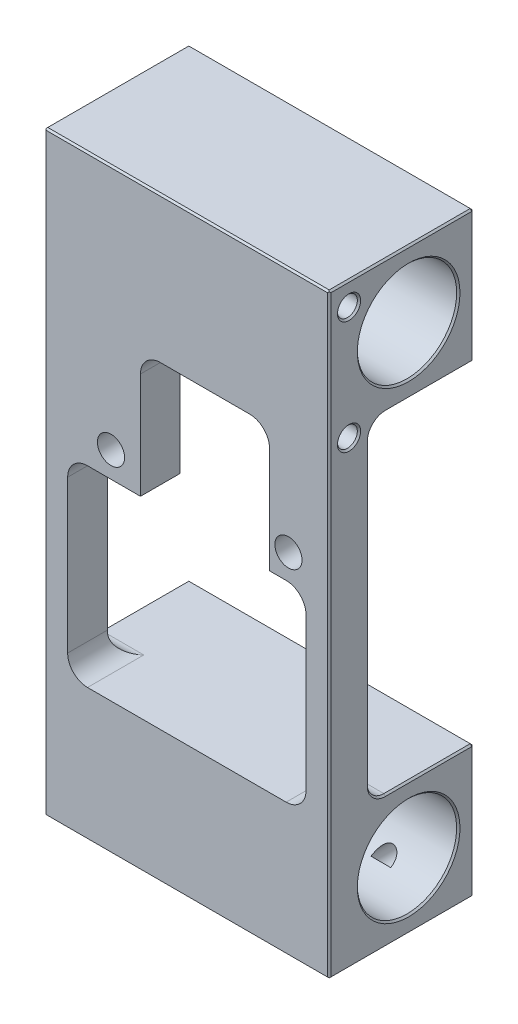
SolidWorks part; units mm, degrees
ref_plane "Спереди" through (0, 0, 0) normal (0, 0, 1) x (1, 0, 0)
ref_plane "Сверху" through (0, 0, 0) normal (0, 1, 0) x (1, 0, 0)
ref_plane "Справа" through (0, 0, 0) normal (1, 0, 0) x (0, 0, -1)
sketch "Model" plane through (0, 0, 0) normal (0, 0, 1) x (1, 0, 0)
  line L0 (0, 90) -> (0, 0)
  line L1 (0, 0) -> (43, 0)
  line L2 (43, 0) -> (43, 90)
  line L3 (43, 90) -> (0, 90)
  line L4 (14.5, 49) -> (14.5, 68)
  line L5 (3.5, 49) -> (14.5, 49)
  line L6 (3.5, 49) -> (3.5, 20)
  line L7 (3.5, 20) -> (39.5, 20)
  line L8 (39.5, 49) -> (39.5, 20)
  line L9 (14.5, 68) -> (34, 68)
  line L10 (34, 68) -> (34, 49)
  line L11 (10.05, 52.85) -> (38.067, 52.85) construction
  line L12 (34, 49) -> (39.5, 49)
  circle A0 centre (10.05, 52.85) radius 2.05
  circle A1 centre (36.85, 52.85) radius 2.05
  dimension "D10" = 4.1
  dimension "D1" = 20
  dimension "D2" = 29
  dimension "D3" = 90
  dimension "D4" = 36
  dimension "D5" = 3.5
  dimension "D6" = 43
  dimension "D7" = 14.5
  dimension "D8" = 9
  dimension "D9" = 22
  dimension "D11" = 4.45
  dimension "D12" = 3.85
  dimension "D13" = 2.85
  dimension "D14" = 26.8
extrude "Бобышка-Вытянуть1" add sketch "Model" along normal blind 21.8
fillet "Скругление1" radius 3 6 edges at (3.5, 20, 10.9) (39.5, 20, 10.9) (39.5, 49, 10.9) (34, 68, 10.9) (14.5, 68, 10.9) (3.5, 49, 10.9)
sketch "Эскиз2" plane through (43, 0, 0) normal (1, 0, 0) x (0, 0, -1)
  line L0 (0, 70) -> (-15.8, 70)
  line L1 (0, 0) -> (0, 90) construction
  line L2 (-15.8, 70) -> (-15.8, 20)
  line L3 (-15.8, 20) -> (0, 20)
  line L4 (-21.8, 90) -> (0, 90) construction
  line L5 (-21.8, 0) -> (0, 0) construction
  line L6 (-21.8, 0) -> (-21.8, 90) construction
  dimension "D1" = 20
  dimension "D2" = 20
  dimension "D3" = 6
extrude "Вырез-Вытянуть1" cut sketch "Эскиз2" against normal through all and the other way through all
fillet "Скругление2" radius 2.5 3 edges at (21.5, 70, 15.8) (39.75, 20, 15.8) (3.25, 20, 15.8)
sketch "Эскиз3" plane through (43, 0, 0) normal (1, 0, 0) x (0, 0, -1)
  line L0 (-21.8, 45) -> (2.0863, 45) construction
  line L1 (-21.8, 0) -> (-21.8, 90) construction
  line L2 (-18.8, 90) -> (-18.8, 38.6194) construction
  line L3 (-21.8, 90) -> (0, 90) construction
  circle A0 centre (-9.8, 80) radius 7.5
  circle A5 centre (-9.8, 10) radius 7.5
  circle A6 centre (-18.8, 86.5) radius 1.5
  circle A7 centre (-18.8, 69.4) radius 1.5
  dimension "D1" = 15
  dimension "D5" = 3
  dimension "D10" = 3
  dimension "D4" = 12
  dimension "D6" = 3
  dimension "D7" = 3.5
  dimension "D9" = 17.1
  dimension "D8" = 2
extrude "Вырез-Вытянуть2" cut sketch "Эскиз3" against normal through all contours A5 | A0 region at (43, 80, 9.8) region at (43, 10, 9.8)
extrude "Вырез-Вытянуть5" cut sketch "Эскиз3<6>" against normal blind 18 contours A6 | A7 region at (43, 86.5, 18.8) region at (43, 69.4, 18.8)
sketch "Эскиз3<6>" plane through (43, 0, 0) normal (1, 0, 0) x (0, 0, -1) same geometry as "Эскиз3"
sketch "Эскиз8" plane through (0, 0, 0) normal (0, 0, -1) x (-1, 0, 0)
  line L0 (-43, 86.5) -> (0, 86.5) construction
  line L1 (-43, 70) -> (-43, 90) construction
  line L2 (-43, 90) -> (0, 90) construction
  line L3 (-21.5, 92.9275) -> (-21.5, 81.0804) construction
  line L4 (0, 90) -> (0, 70) construction
  line L5 (-55.1775, 45) -> (12.5287, 45) construction
  line L6 (0, 0) -> (-43, 0) construction
  line L7 (-43, 0) -> (-43, 20) construction
  circle A0 centre (-35, 86.5) radius 1.5
  circle A1 centre (-8, 86.5) radius 1.5
  circle A2 centre (-8, 3.5) radius 1.5
  circle A3 centre (-35, 3.5) radius 1.5
  dimension "D2" = 3
  dimension "D1" = 3.5
  dimension "D3" = 8
  dimension "D4" = 8
  dimension "D5" = 3.5
  dimension "D6" = 8
extrude "Вырез-Вытянуть7" cut sketch "Эскиз8" against normal blind 6
chamfer "Фаска3" distance 0.25 angle 45 34 edges at (33.5, 86.5, 0) (9.5, 86.5, 0) (36.5, 3.5, 0) (6.5, 3.5, 0) (0, 17.5, 9.8) (0, 87.5, 9.8) (21.5, 90, 0) (21.5, 70, 0) (21.5, 0, 0) (0, 80, 0) (0, 90, 10.9) (0, 45, 21.8) (0, 0, 10.9) (0, 10, 0) (0, 70, 6.65) (0, 69.2678, 15.0678) (0, 45, 15.8) (0, 20.7322, 15.0678) (0, 20, 6.65) (21.5, 20, 0) (43, 69.2678, 15.0678) (43, 45, 15.8) (43, 20.7322, 15.0678) (43, 20, 6.65) (43, 10, 0) (43, 0, 10.9) (43, 45, 21.8) (43, 90, 10.9) (43, 80, 0) (43, 70, 6.65) (43, 17.5, 9.8) (43, 87.5, 9.8) (43, 88, 18.8) (43, 70.9, 18.8)
chamfer "Фаска4" distance 0.25 angle 45 2 edges at (21.5, 90, 21.8) (21.5, 0, 21.8)
equation "\"D12@Model\"=( \"D10@Model\" / 2 )+1.8"
equation "\"D13@Model\"=( \"D10@Model\" / 2 ) + 0.8"
